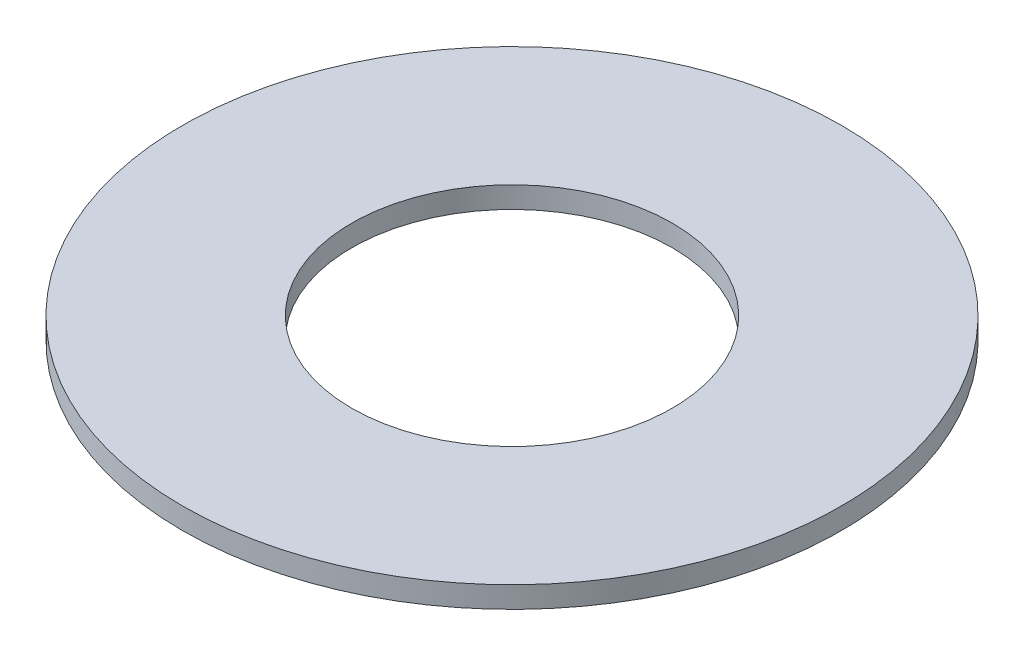
SolidWorks part; units mm, degrees
ref_plane "Front Plane" through (0, 0, 0) normal (0, 0, 1) x (1, 0, 0)
ref_plane "Top Plane" through (0, 0, 0) normal (0, 1, 0) x (1, 0, 0)
ref_plane "Right Plane" through (0, 0, 0) normal (1, 0, 0) x (0, 0, -1)
sketch "Sketch1" plane through (0, 0, 0) normal (0, 1, 0) x (1, 0, 0)
  circle A0 centre (0, 0) radius 92.5
  dimension "FLANGE_OD" = 185
extrude "Boss-Extrude1" add sketch "Sketch1" along normal blind 6
sketch "Sketch2" plane through (0, 0, 0) normal (0, 1, 0) x (1, 0, 0)
  circle A0 centre (0, 0) radius 45
  dimension "BORE_D" = 90
extrude "Cut-Extrude1" cut sketch "Sketch2" along normal through all
sketch "Sketch3" plane through (0, 6, 0) normal (0, 1, 0) x (1, 0, 0)
  circle A0 centre (0, 0) radius 26.4876 construction
  circle A1 centre (-26.4876, 0) radius 5.1077
  dimension "BOLT_D" = 10.2155
  dimension "BOLT_PCD" = 52.9752
extrude "Cut-Extrude2" cut sketch "Sketch3" against normal blind 5.3053 rebuild error yes
pattern_circular "CirPattern1" count 6 over 360 rebuild error yes
